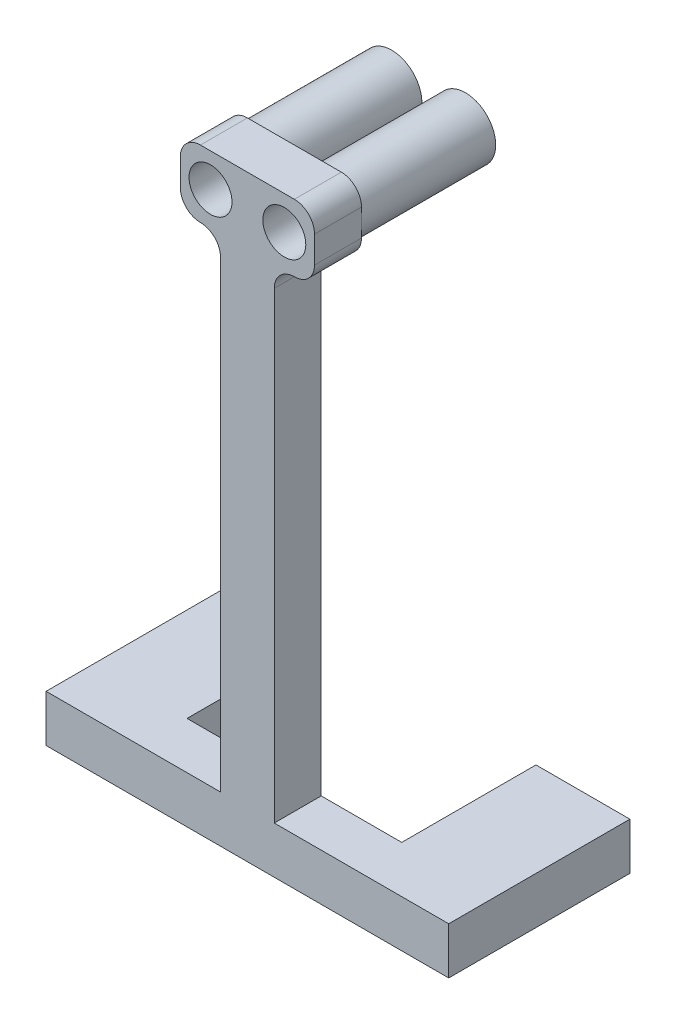
SolidWorks part; units mm, degrees
material "ABS"
ref_plane "Front Plane" through (0, 0, 0) normal (0, 0, 1) x (1, 0, 0)
ref_plane "Top Plane" through (0, 0, 0) normal (0, 1, 0) x (1, 0, 0)
ref_plane "Right Plane" through (0, 0, 0) normal (1, 0, 0) x (0, 0, -1)
sketch "Sketch1" plane through (0, 0, 0) normal (0, 0, 1) x (1, 0, 0)
  line L1 (-38.1, 4.445) -> (38.1, 4.445)
  line L2 (-38.1, 4.445) -> (-38.1, -4.445)
  line L3 (-38.1, -4.445) -> (38.1, -4.445)
  line L4 (38.1, 4.445) -> (38.1, -4.445)
  line L5 (-38.1, 4.445) -> (38.1, -4.445) construction
  line L6 (-38.1, -4.445) -> (38.1, 4.445) construction
  line L7 (-5.08, 95.885) -> (5.08, 95.885)
  line L8 (-5.08, 95.885) -> (-5.08, 4.445)
  line L9 (-5.08, 4.445) -> (5.08, 4.445)
  line L10 (5.08, 95.885) -> (5.08, 4.445)
  line L11 (-5.08, 95.885) -> (5.08, 4.445) construction
  line L12 (-5.08, 4.445) -> (5.08, 95.885) construction
  line L13 (-12.7, 108.585) -> (12.7, 108.585)
  line L14 (-12.7, 108.585) -> (-12.7, 95.885)
  line L15 (-12.7, 95.885) -> (12.7, 95.885)
  line L16 (12.7, 108.585) -> (12.7, 95.885)
  line L17 (-12.7, 108.585) -> (12.7, 95.885) construction
  line L18 (-12.7, 95.885) -> (12.7, 108.585) construction
  circle A0 centre (-6.985, 102.235) radius 4.064
  circle A1 centre (6.985, 102.235) radius 4.064
  point P0 (0, 0)
  point P6 (0, 50.165)
  point P11 (0, 102.235)
  point P22 (0, 95.885)
  point P23 (0, 95.885)
  point P25 (0, 4.445)
  point P26 (0, 4.445)
  dimension "D4" = 8.128
  dimension "D1" = 8.89
  dimension "D2" = 91.44
  dimension "D3" = 10.16
  dimension "D5" = 6.985
  dimension "D6" = 6.985
  dimension "D7" = 25.4
  dimension "D8" = 12.7
  dimension "D9" = 76.2
extrude "Boss-Extrude1" add sketch "Sketch1" along normal blind 8.89 contours L10 L7 L8 L1 | L16 L13 L14 L15 L7 A1 A0 | L4 L1 L2 L3 region at (0, 0, 0) region at (0, 50.165, 0) region at (0, 102.235, 0)
sketch "Sketch2" plane through (0, 0, 0) normal (0, 0, -1) x (-1, 0, 0)
  line L0 (-12.7, 108.585) -> (-12.7, 95.885) construction
  line L1 (12.7, 108.585) -> (12.7, 95.885) construction
  circle A0 centre (6.985, 102.235) radius 5.715
  circle A1 centre (-6.985, 102.235) radius 5.715
extrude "Boss-Extrude2" add sketch "Sketch2" along normal blind 25.4
sketch "Sketch3" plane through (0, 0, -25.4) normal (0, 0, -1) x (-1, 0, 0)
  circle A0 centre (6.985, 102.235) radius 4.445
  circle A1 centre (-6.985, 102.235) radius 4.445
  circle A2 centre (-6.985, 102.235) radius 5.715 construction
  dimension "D1" = 8.89
extrude "Cut-Extrude1" cut sketch "Sketch3" against normal blind 25.4
fillet "Fillet1" radius 3.81 6 edges at (-5.08, 95.885, 4.445) (-12.7, 95.885, 4.445) (5.08, 95.885, 4.445) (12.7, 95.885, 4.445) (12.7, 108.585, 4.445) (-12.7, 108.585, 4.445)
sketch "Sketch4" plane through (0, 0, 0) normal (0, 0, -1) x (-1, 0, 0)
  line L0 (38.1, -4.445) -> (-38.1, -4.445) construction
  line L1 (-38.1, 4.445) -> (-20.32, 4.445)
  line L2 (-38.1, 4.445) -> (-38.1, -4.445)
  line L3 (-38.1, -4.445) -> (-20.32, -4.445)
  line L4 (-20.32, 4.445) -> (-20.32, -4.445)
  line L5 (38.1, 4.445) -> (5.08, 4.445) construction
  line L6 (38.1, -4.445) -> (20.32, -4.445)
  line L7 (38.1, -4.445) -> (38.1, 4.445)
  line L8 (38.1, 4.445) -> (20.32, 4.445)
  line L9 (20.32, -4.445) -> (20.32, 4.445)
  line L10 (-5.08, 4.445) -> (-38.1, 4.445) construction
  dimension "D1" = 17.78
  dimension "D2" = 17.78
extrude "Boss-Extrude3" add sketch "Sketch4" along normal blind 25.4
